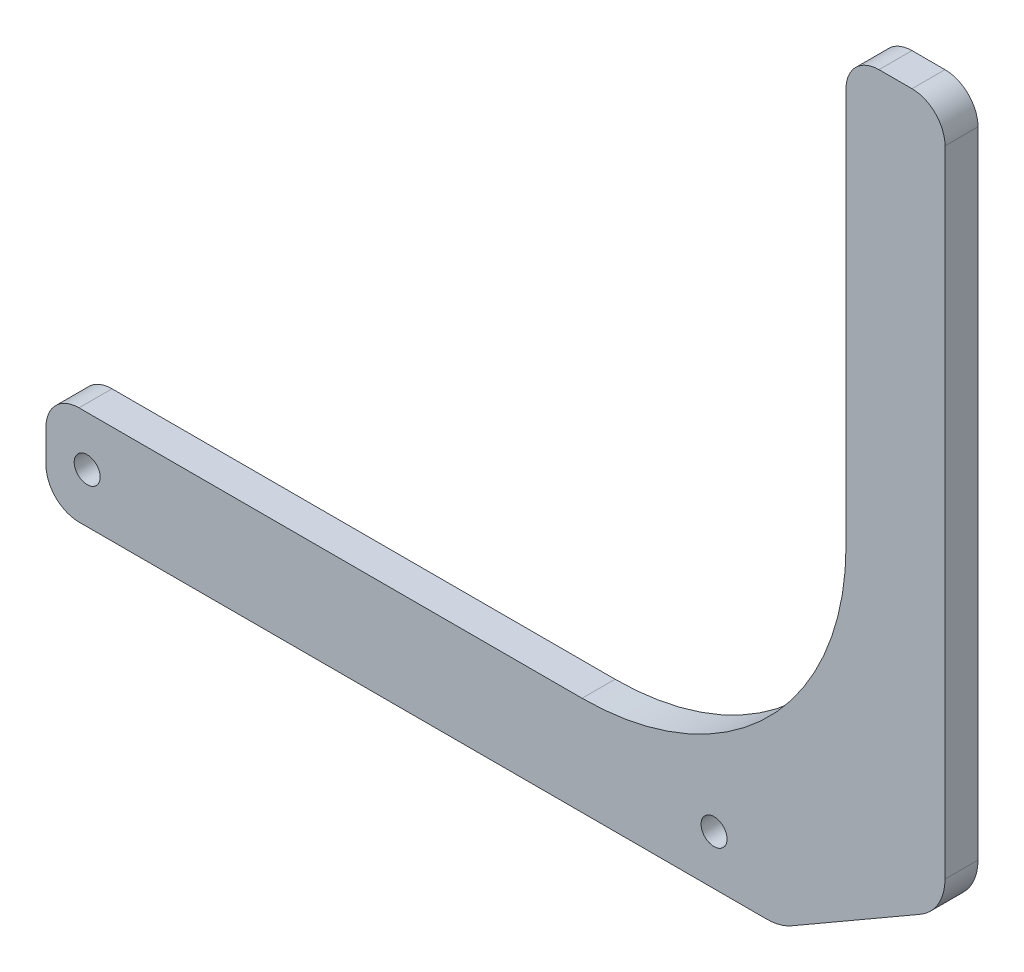
SolidWorks part; units mm, degrees
material "AISI 304"
ref_plane "Front Plane" through (0, 0, 0) normal (0, 0, 1) x (1, 0, 0)
ref_plane "Top Plane" through (0, 0, 0) normal (0, 1, 0) x (1, 0, 0)
ref_plane "Right Plane" through (0, 0, 0) normal (1, 0, 0) x (0, 0, -1)
sketch "Sketch1" plane through (0, 0, 0) normal (0, 0, 1) x (1, 0, 0)
  line L0 (-88.9, -9.525) -> (88.9, 9.525) construction
  line L1 (-88.9, 9.525) -> (69.85, 9.525)
  line L2 (-88.9, 9.525) -> (-88.9, -9.525)
  line L3 (-88.9, -9.525) -> (88.9, -9.525)
  line L4 (88.9, 9.525) -> (88.9, -9.525)
  line L5 (88.9, 9.525) -> (88.9, 142.875)
  line L6 (69.85, 9.525) -> (69.85, 142.875)
  line L7 (69.85, 142.875) -> (88.9, 142.875)
  point P8 (-88.9, 0)
  dimension "D1" = 19.05
  dimension "D2" = 177.8
  dimension "D3" = 152.4
  dimension "D4" = 19.05
sheet metal parameters "Sheet-Metal1" thickness 6.35 parameters "D1"=1.5875
base flange "Base-Flange1" sketch "Sketch1" thickness 6.35 reverse thickness direction yes parameters "D1"=1.5875
hole_wizard "M6x1.0 Tapped Hole1" positions "Sketch4" profile "Sketch3" tap size "M6x1.0" standard "ANSI Metric" end condition up to next
sketch "Sketch4" plane through (0, 0, 6.35) normal (0, 0, 1) x (1, 0, 0)
  line L0 (-88.9, 9.525) -> (-88.9, -9.525) construction
  line L1 (-88.9, -9.525) -> (88.9, -9.525) construction
  line L2 (-76.2, 0) -> (44.45, 0) construction
  point P0 (-76.2, 0)
  point P1 (44.45, 0)
  dimension "D1" = 12.7
  dimension "D2" = 120.65
  dimension "D5" = 9.525
sketch "Sketch3" plane through (-76.2, 0, 6.35) normal (1, 0, 0) x (0, -1, 0)
  line L0 (0, 0) -> (0, 6.35)
  line L1 (0, 6.35) -> (2.5, 6.35)
  line L2 (2.5, 6.35) -> (2.5, 0)
  line L5 (2.5, 0) -> (0, 0)
  line L11 (0, -6.35) -> (0, 107.95) construction
  dimension "Thru Tap Drill Dia." = 5
  dimension "Thru Tap Drill Depth" = 6.35
cosmetic thread "Hole Thread1" parameters "D2"=6
cosmetic thread "Hole Thread2" parameters "D2"=6
chamfer "Chamfer1" distance 31.75 angle 30 1 edges at (88.9, -9.525, 3.175) first distance on face at (0, -9.525, 3.175)
sketch "Sketch5" plane through (0, 0, 6.35) normal (0, 0, 1) x (1, 0, 0)
  line L0 (-88.9, -9.525) -> (57.15, -9.525) construction
  line L1 (-88.9, 9.525) -> (-84.1248, 9.525)
  line L2 (-88.9, 9.525) -> (-88.9, -9.525)
  line L3 (-88.9, -9.525) -> (-84.1248, -9.525)
  line L4 (-84.1248, 9.525) -> (-84.1248, -9.525)
  dimension "D1" = 4.7752
extrude "Extrude1" cut sketch "Sketch5" against normal up to next normal cut yes
fillet "Fillet1" radius 6.35 4 edges at (-84.1248, -9.525, 3.175) (-84.1248, 9.525, 3.175) (88.9, 142.875, 3.175) (69.85, 142.875, 3.175)
fillet "Fillet2" radius 50.8 1 edges at (69.85, 9.525, 3.175)
fillet "Fillet3" radius 9.525 2 edges at (88.9, 8.8059, 3.175) (57.15, -9.525, 3.175)
flat pattern "Flat-Pattern1" [suppressed]
sketch "Bend-Lines1" plane through (0, 0, 0) normal (0, 1, 0) x (-1, 0, 0)
